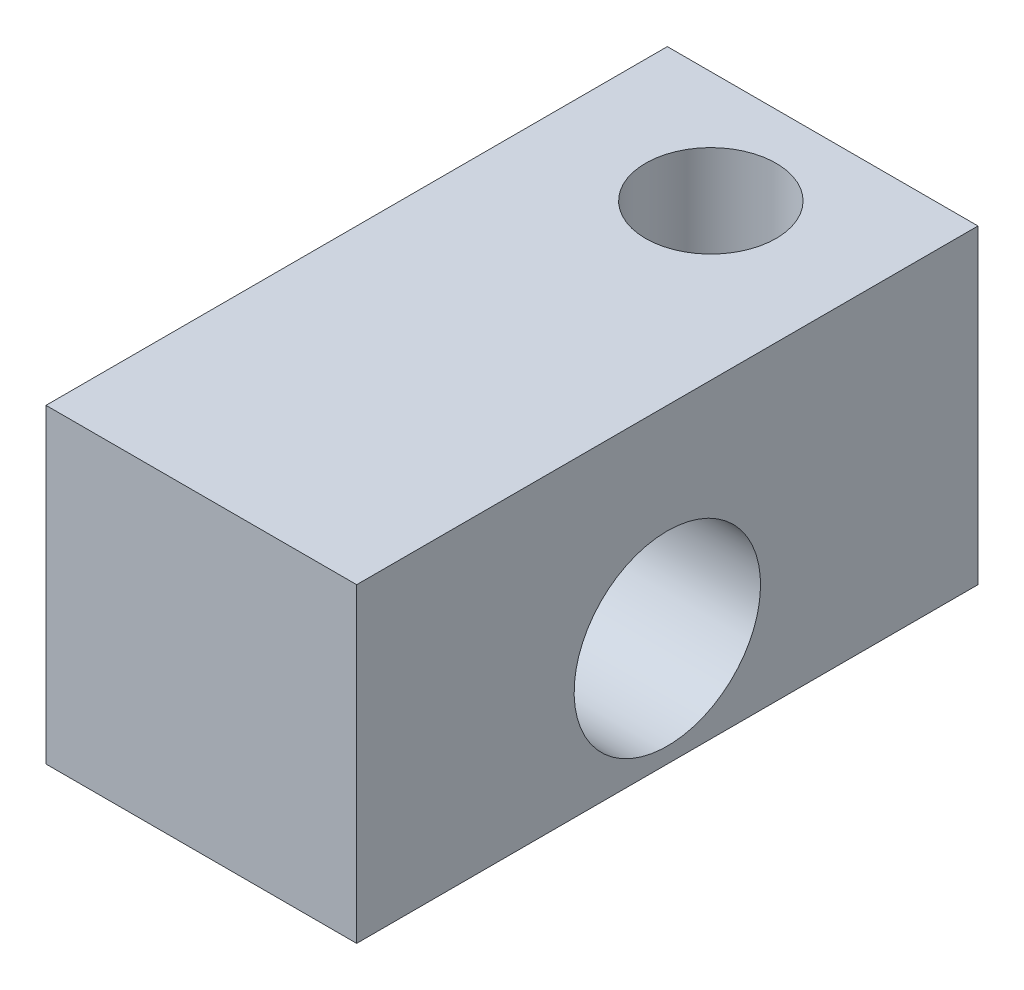
SolidWorks part; units mm, degrees
ref_plane "Front Plane" through (0, 0, 0) normal (0, 0, 1) x (1, 0, 0)
ref_plane "Top Plane" through (0, 0, 0) normal (0, 1, 0) x (1, 0, 0)
ref_plane "Right Plane" through (0, 0, 0) normal (1, 0, 0) x (0, 0, -1)
sketch "Sketch1" plane through (0, 0, 0) normal (0, 0, 1) x (1, 0, 0)
  line L1 (0, 0) -> (5, 0)
  line L2 (0, 0) -> (0, -5)
  line L3 (0, -5) -> (5, -5)
  line L4 (5, 0) -> (5, -5)
  dimension "D1" = 5
  dimension "D2" = 5
extrude "Boss-Extrude1" add sketch "Sketch1" along normal blind 10
sketch "Sketch2" plane through (5, 0, 0) normal (1, 0, 0) x (0, 0, -1)
  line L0 (-10, -5) -> (0, -5) construction
  line L1 (-5, -3.25) -> (-5, -5) construction
  circle A0 centre (-5, -3.25) radius 1.5
  dimension "D1" = 3
  dimension "D2" = 1.75
extrude "Cut-Extrude1" cut sketch "Sketch2" against normal up to next
sketch "Sketch3" plane through (0, 0, 0) normal (0, 1, 0) x (1, 0, 0)
  line L0 (5, -10) -> (5, 0) construction
  line L1 (5, 0) -> (0, 0) construction
  circle A0 centre (2.5, -1.8) radius 1.05
  dimension "D1" = 2.5
  dimension "D3" = 2.1
  dimension "D2" = 1.8
extrude "Cut-Extrude2" cut sketch "Sketch3" against normal blind 3.25
sketch "Sketch4" plane through (0, -5, 0) normal (0, -1, 0) x (1, 0, 0)
  line L0 (2.5, 9.25) -> (2.5, 10) construction
  line L1 (0, 10) -> (5, 10) construction
  circle A0 centre (2.5, 8.2) radius 1.05
  dimension "D2" = 2.1
  dimension "D1" = 0.75
extrude "Cut-Extrude3" cut sketch "Sketch4" against normal blind 1.75
